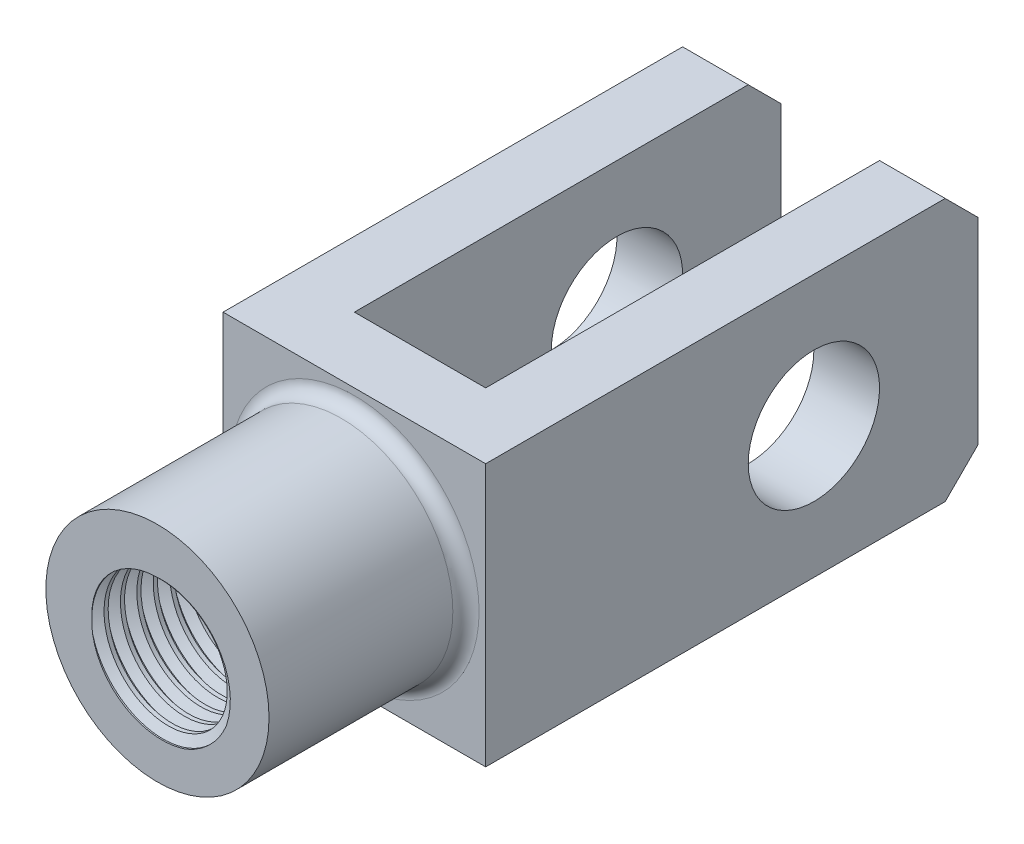
SolidWorks part; units mm, degrees
ref_plane "Front Plane" through (0, 0, 0) normal (0, 0, 1) x (1, 0, 0)
ref_plane "Top Plane" through (0, 0, 0) normal (0, 1, 0) x (1, 0, 0)
ref_plane "Right Plane" through (0, 0, 0) normal (1, 0, 0) x (0, 0, -1)
sketch "Sketch1" plane through (0, 0, 0) normal (0, 0, 1) x (1, 0, 0)
  circle A0 centre (0, 0) radius 17
  dimension "D1" = 34
extrude "Boss-Extrude1" add sketch "Sketch1" along normal blind 30
sketch "Sketch2" plane through (0, 0, 0) normal (0, 0, -1) x (-1, 0, 0)
  line L1 (-20, -20) -> (20, -20)
  line L2 (-20, -20) -> (-20, 20)
  line L3 (-20, 20) -> (20, 20)
  line L4 (20, -20) -> (20, 20)
  line L5 (-20, -20) -> (20, 20) construction
  line L6 (-20, 20) -> (20, -20) construction
  point P0 (0, 0)
  dimension "D1" = 40
  dimension "D2" = 40
extrude "Boss-Extrude2" add sketch "Sketch2" along normal blind 75
sketch "Sketch3" plane through (0, 20, 0) normal (0, 1, 0) x (1, 0, 0)
  line L0 (-10, 75) -> (-10, 10)
  line L1 (-20, 75) -> (20, 75) construction
  line L2 (-20, 75) -> (-20, 0) construction
  line L3 (-20, 0) -> (20, 0) construction
  line L4 (20, 75) -> (20, 0) construction
  line L5 (-20, 75) -> (20, 0) construction
  line L6 (-20, 0) -> (20, 75) construction
  line L7 (-10, 10) -> (10, 10)
  line L8 (10, 10) -> (10, 75)
  line L9 (-10, 75) -> (10, 75)
  point P4 (0, 37.5)
  dimension "D1" = 20
  dimension "D2" = 10
  dimension "D3" = 65
extrude "Cut-Extrude1" cut sketch "Sketch3" against normal blind 75 contours L8 L9 L0 L7
chamfer "Chamfer1" distance 5 angle 45 4 edges at (-15, -20, -75) (15, -20, -75) (-15, 20, -75) (15, 20, -75)
sketch "Sketch4" plane through (-20, 0, 0) normal (-1, 0, 0) x (0, 0, 1)
  line L6 (-75, 15) -> (-75, -15)
  line L7 (-75, -15) -> (-70, -20)
  line L8 (-70, -20) -> (0, -20)
  line L9 (0, -20) -> (0, 20)
  line L10 (0, 20) -> (-70, 20)
  line L11 (-70, 20) -> (-75, 15)
  line L12 (-75, 15) -> (-75, -15) construction
  line L13 (-75, -15) -> (-70, -20) construction
  line L14 (-70, -20) -> (0, -20) construction
  line L15 (0, -20) -> (0, 20) construction
  line L16 (0, 20) -> (-70, 20) construction
  line L17 (-70, 20) -> (-75, 15) construction
  circle A0 centre (-50, 0) radius 10
  dimension "D3" = 20
  dimension "D2" = 20
  dimension "D4" = 25
  dimension "D1" = 0
extrude "Cut-Extrude2" cut sketch "Sketch4" against normal through all
fillet "Fillet1" radius 2 1 edges at (17, 0, 0)
sketch "Sketch7" plane through (0, 0, 30) normal (0, 0, 1) x (1, 0, 0)
  circle A0 centre (0, 0) radius 10
  dimension "D1" = 20
extrude "Cut-Extrude3" cut sketch "Sketch7" against normal blind 23
thread "Thread1" pitch 2.5 start angle 0, offset 2.5, length 23, pitch 2.5, diameter 20
ref_plane "Plane1" through (-10, 0, 32.5) normal (0, -1, 0) x (-1, 0, 0)
sketch "Thread Profile1" plane through (-10, 0, 32.5) normal (0, -1, 0) x (-1, 0, 0)
  line L0 (0, 0) -> (0, 2.5) construction
  line L1 (0, 0) -> (1.3532, 0.7812)
  line L2 (1.3532, 0.7812) -> (1.3532, 1.0937)
  line L3 (1.3532, 1.0937) -> (0, 1.875)
  line L4 (1.3532, 0.9375) -> (0, 0.9375) construction
  line L11 (0, 0) -> (0, 1.875)
  point P2 (0, 0)
  dimension "Pitch" = 2.5
  dimension "Profile_Angle" = 60
  dimension "Profile_Land" = 0.3125
  dimension "Profile_Height" = 1.3532
